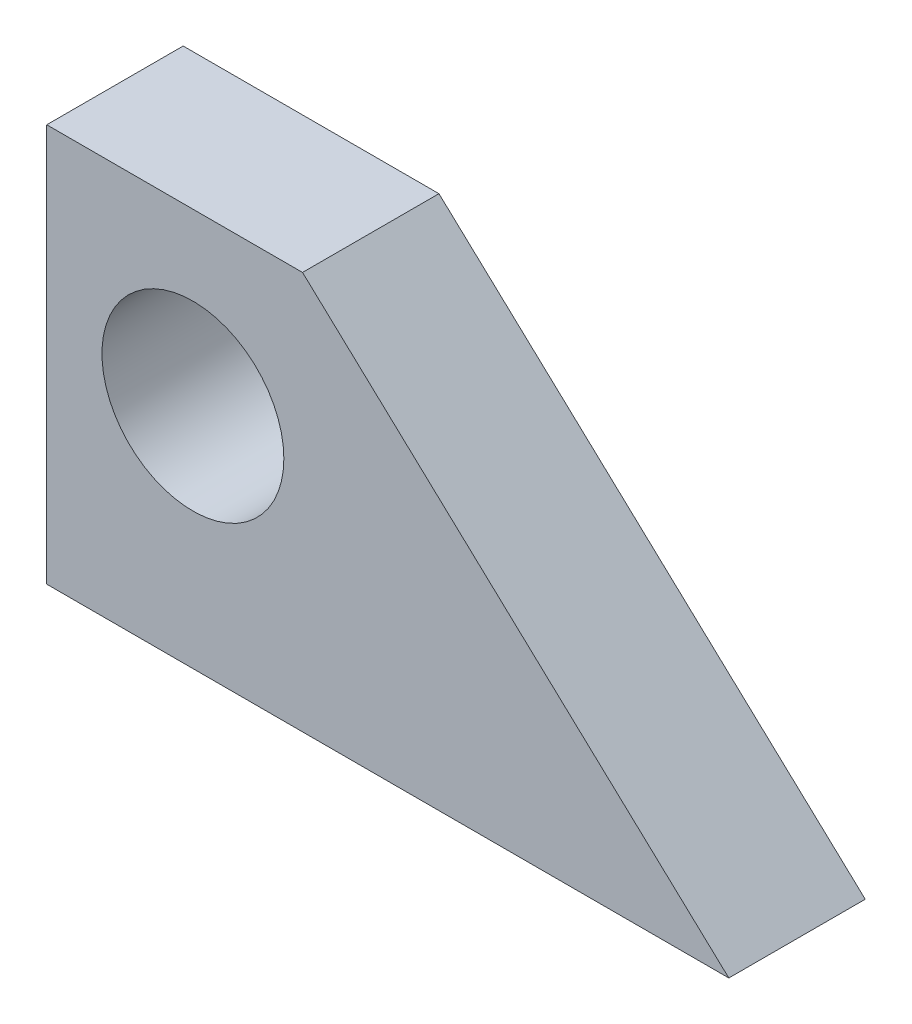
SolidWorks part; units mm, degrees
ref_plane "Front Plane" through (0, 0, 0) normal (0, 0, 1) x (1, 0, 0)
ref_plane "Top Plane" through (0, 0, 0) normal (0, 1, 0) x (1, 0, 0)
ref_plane "Right Plane" through (0, 0, 0) normal (1, 0, 0) x (0, 0, -1)
sketch "Sketch1" plane through (0, 0, 0) normal (0, 0, 1) x (1, 0, 0)
  line L0 (8.5714, -10) -> (23.5714, -10)
  line L1 (-6.4286, 7.5) -> (4.8214, 7.5)
  line L2 (-6.4286, 7.5) -> (-6.4286, -10)
  line L3 (-6.4286, -10) -> (8.5714, -10)
  line L5 (-6.4286, 7.5) -> (8.5714, -10) construction
  line L6 (-6.4286, -10) -> (4.8214, 7.5) construction
  line L7 (23.5714, -10) -> (4.8214, 7.5)
  point P0 (0, 0)
  dimension "D1" = 7.5
  dimension "D2" = 15
  dimension "D3" = 15
  dimension "D4" = 10
extrude "Boss-Extrude1" add sketch "Sketch1" along normal blind 3 and the other way blind 3
sketch "Sketch2" plane through (0, 0, 3) normal (0, 0, 1) x (1, 0, 0)
  circle A0 centre (0, 0) radius 4
  dimension "D1" = 8
extrude "Cut-Extrude1" cut sketch "Sketch2" against normal blind 10
